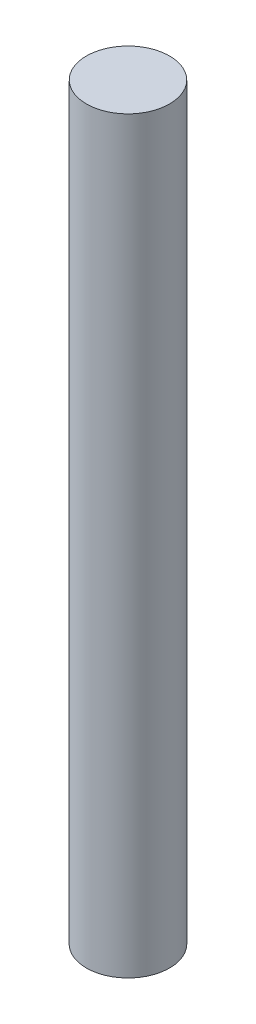
SolidWorks part; units mm, degrees
ref_plane "Front Plane" through (0, 0, 0) normal (0, 0, 1) x (1, 0, 0)
ref_plane "Top Plane" through (0, 0, 0) normal (0, 1, 0) x (1, 0, 0)
ref_plane "Right Plane" through (0, 0, 0) normal (1, 0, 0) x (0, 0, -1)
sketch "Sketch2" plane through (0, 0, 0) normal (0, 1, 0) x (1, 0, 0)
  circle A0 centre (0, 0) radius 3.175
  dimension "D1" = 6.35
extrude "Boss-Extrude1" add sketch "Sketch2" along normal mid plane 57.15
